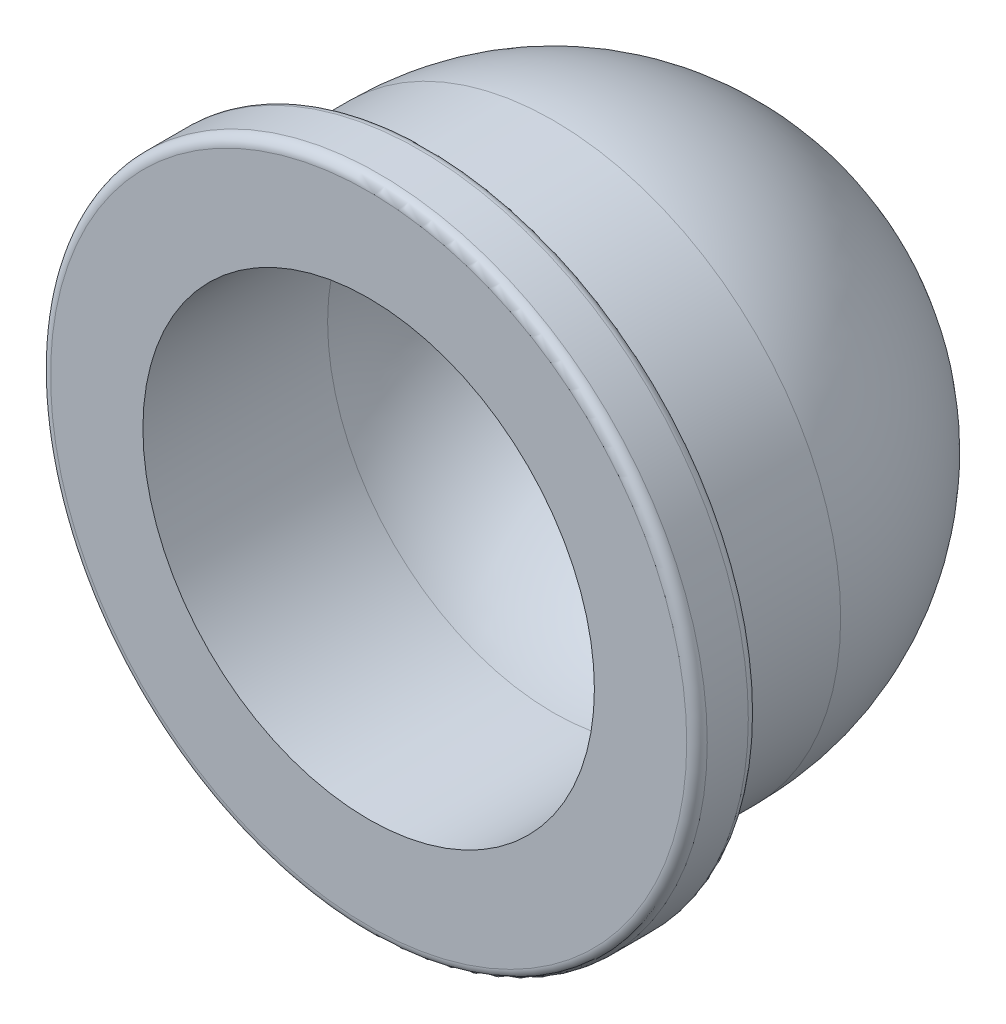
SolidWorks part; units mm, degrees
ref_plane "Front Plane" through (0, 0, 0) normal (0, 0, 1) x (1, 0, 0)
ref_plane "Top Plane" through (0, 0, 0) normal (0, 1, 0) x (1, 0, 0)
ref_plane "Right Plane" through (0, 0, 0) normal (1, 0, 0) x (0, 0, -1)
sketch "Sketch2" plane through (0, 0, 0) normal (0, 0, 1) x (1, 0, 0)
  circle A0 centre (0, 0) radius 7
  dimension "D1" = 14
extrude "Boss-Extrude1" add sketch "Sketch2" along normal blind 10 contours A0
sketch "Sketch3" plane through (0, 0, 10) normal (0, 0, 1) x (1, 0, 0)
  circle A0 centre (0, 0) radius 8
  dimension "D1" = 16
extrude "Boss-Extrude2" add sketch "Sketch3" along normal blind 1.5
fillet "Fillet3" radius 7 1 edges at (7, 0, 0)
shell "Shell1" thickness 1.5 removed face at (8, 0, 11.5)
fillet "Fillet4" radius 0.25 2 edges at (8, 0, 10) (8, 0, 11.5)
